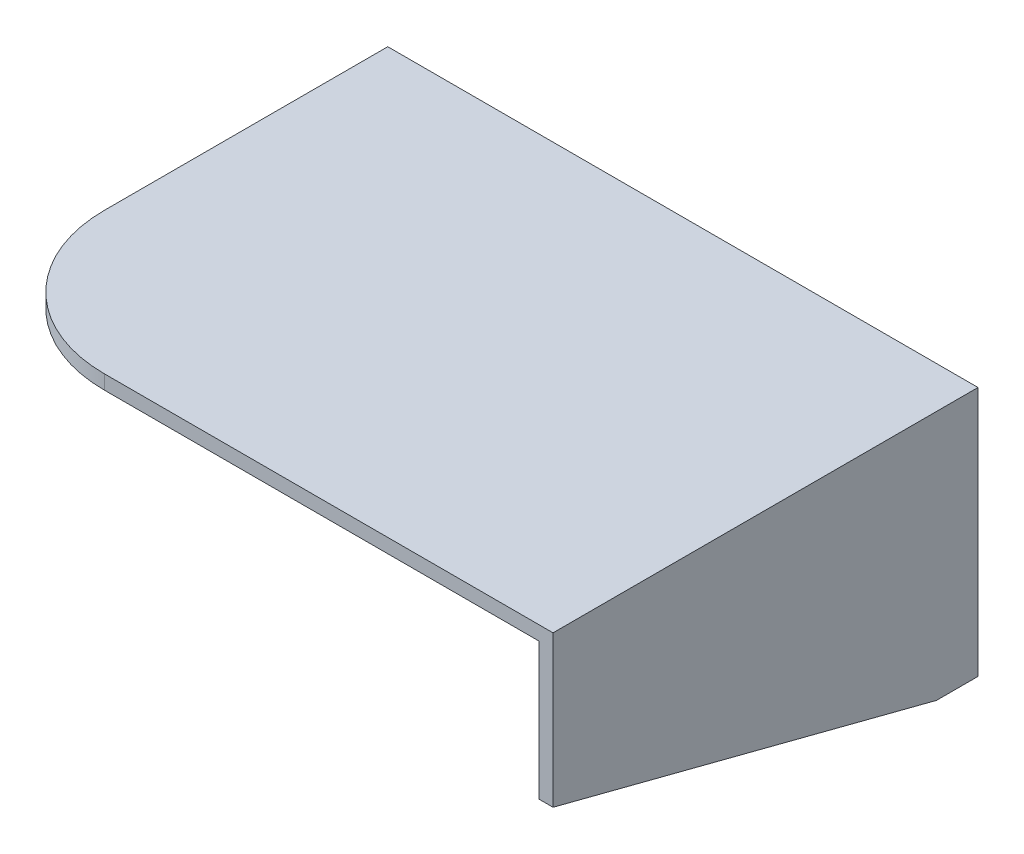
SolidWorks part; units mm, degrees
ref_plane "Front Plane" through (0, 0, 0) normal (0, 0, 1) x (1, 0, 0)
ref_plane "Top Plane" through (0, 0, 0) normal (0, 1, 0) x (1, 0, 0)
ref_plane "Right Plane" through (0, 0, 0) normal (1, 0, 0) x (0, 0, -1)
sketch "Sketch2" plane through (0, 0, 0) normal (0, 0, 1) x (1, 0, 0)
  line L0 (0, 4.05) -> (2.5, 4.05)
  line L1 (0, -4.05) -> (10.5, -4.05)
  line L2 (2.5, 4.05) -> (2.5, 30.95)
  line L3 (2.5, 30.95) -> (-49.5, 30.95)
  line L4 (-49.5, 30.95) -> (-49.5, 33.95)
  line L5 (-49.5, 33.95) -> (10.5, 33.95)
  line L6 (10.5, 33.95) -> (10.5, -4.05)
  line L7 (2.5, 30.95) -> (10.5, 30.95)
  line L8 (10.5, 33.95) -> (75.5, 33.95)
  line L9 (75.5, 33.95) -> (75.5, -19.05)
  line L10 (75.5, -19.05) -> (10.5, -19.05)
  line L11 (10.5, -19.05) -> (10.5, -4.05)
  line L12 (10.5, 30.95) -> (72.5, 30.95)
  line L13 (30.5, 33.95) -> (30.5, 30.95)
  line L14 (72.5, 30.95) -> (72.5, -19.05)
  point P4 (0, 0)
  line B0 (0, -7.95) -> (-2.04, -7.95)
  line B1 (-6.1524, -4.048) -> (-6.1524, 4.048)
  line B2 (-2.04, 7.95) -> (0, 7.95)
  line B3 (0, 7.95) -> (0, -7.95)
  line B4 (-2.04, -7.95) -> (-6.1524, -4.048)
  line B5 (-6.1524, 4.048) -> (-2.04, 7.95)
  line B6 (0, -4.05) -> (0, 4.05) construction
  dimension "D1" = 10.5
  dimension "D2" = 8
  dimension "D3" = 3
  dimension "D4" = 60
  dimension "D5" = 35
  dimension "D6" = 65
  dimension "D7" = 50
  dimension "D8" = 20
  dimension "D9" = 3
sketch_block_instance "Extrusion Profile-1"
sketch_block "Block1" parameters "D1"=8.44, "D2"=2.6, "D3"=6, "D4"=16.7, "D6"=5.6686, "D7"=2.0404, "D8"=8.0963, "D9"=15.9, "D5"=2.4157
extrude "Boss-Extrude1" add sketch "Sketch2" along normal blind 6 contours L0 B3 L1 L6 L7 L2 | B2 B5 B1 B4 B0 B3 region at (-2.7416, 0, 0) region at (6.1459, 12.5429, 0)
extrude "Boss-Extrude2" add sketch "Sketch2<3>" along normal blind 90 contours L3 L7 L6 L5 L4 | L13 L8 L6 | L12 L14 L10 L9 L8 L13 region at (-19.5, 32.45, 0) region at (20.5, 32.45, 0) region at (31.1953, 32.45, 0)
sketch "Sketch2<3>" plane through (0, 0, 0) normal (0, 0, 1) x (1, 0, 0) same geometry as "Sketch2"
extrude "Boss-Extrude3" add sketch "Sketch2<4>" along normal blind 3 contours L6 L11 L10 L9 | L8 L13 L9 region at (41.5, 5.95, 0) region at (31.1953, 32.45, 0)
sketch "Sketch2<4>" plane through (0, 0, 0) normal (0, 0, 1) x (1, 0, 0) same geometry as "Sketch2"
fillet "Fillet1" radius 3 1 edges at (10.5, 13.45, 3)
fillet "Fillet2" radius 3 1 edges at (10.5, 13.45, 6)
fillet "Fillet3" radius 30 1 edges at (-49.5, 32.45, 90)
sketch "Sketch3" plane through (0, 0, 0) normal (0, 0, -1) x (-1, 0, 0)
  line L0 (-2.5, 4.05) -> (-2.5, -4.05)
  line L1 (0, -4.05) -> (-10.5, -4.05) construction
  line L18 (49.5, 33.95) -> (-75.5, 33.95)
  line L19 (-75.5, 33.95) -> (-75.5, -19.05)
  line L20 (-75.5, -19.05) -> (-10.5, -19.05)
  line L21 (-10.5, -19.05) -> (-10.5, -4.05)
  line L22 (-10.5, -4.05) -> (0, -4.05)
  line L23 (0, -4.05) -> (0, -7.95)
  line L24 (0, -7.95) -> (2.04, -7.95)
  line L25 (2.04, -7.95) -> (6.1524, -4.048)
  line L26 (6.1524, -4.048) -> (6.1524, 4.048)
  line L27 (6.1524, 4.048) -> (2.04, 7.95)
  line L28 (2.04, 7.95) -> (0, 7.95)
  line L29 (0, 7.95) -> (0, 4.05)
  line L30 (0, 4.05) -> (-2.5, 4.05)
  line L31 (-2.5, 4.05) -> (-2.5, 30.95)
  line L32 (-2.5, 30.95) -> (49.5, 30.95)
  line L33 (49.5, 30.95) -> (49.5, 33.95)
  line L34 (49.5, 33.95) -> (-75.5, 33.95)
  line L35 (-75.5, 33.95) -> (-75.5, -19.05)
  line L36 (-75.5, -19.05) -> (-10.5, -19.05)
  line L37 (-10.5, -19.05) -> (-10.5, -4.05)
  line L38 (-10.5, -4.05) -> (-2.5, -4.05)
  line L47 (-2.5, 4.05) -> (-2.5, 30.95)
  line L48 (-2.5, 30.95) -> (49.5, 30.95)
  line L49 (49.5, 30.95) -> (49.5, 33.95)
  dimension "D1" = 0
sketch "Sketch4" plane through (0, 0, 0) normal (0, 0, -1) x (-1, 0, 0)
  line L0 (6.1524, 1) -> (6.1524, -1)
  line L1 (6.1524, -4.048) -> (6.1524, 4.048) construction
  line L2 (6.1524, -1) -> (2.1524, -1)
  line L3 (2.1524, -1) -> (2.1524, 1)
  line L4 (2.1524, 1) -> (6.1524, 1)
  point P5 (6.1524, 0)
  dimension "D1" = 2
  dimension "D2" = 4
extrude "Cut-Extrude1" cut sketch "Sketch4" against normal through all
sketch "Sketch5" plane through (75.5, 0, 0) normal (1, 0, 0) x (0, 0, -1)
  line L0 (-8.799, -19.05) -> (-90, 1.95)
  line L1 (-90, -19.05) -> (0, -19.05) construction
  line L2 (-90, 33.95) -> (-90, -19.05) construction
  line L3 (-90, 1.95) -> (-90, -19.05)
  line L4 (-90, -19.05) -> (-8.799, -19.05)
  dimension "D1" = 21
  dimension "D2" = 14.5
extrude "Cut-Extrude2" cut sketch "Sketch5" against normal through all
